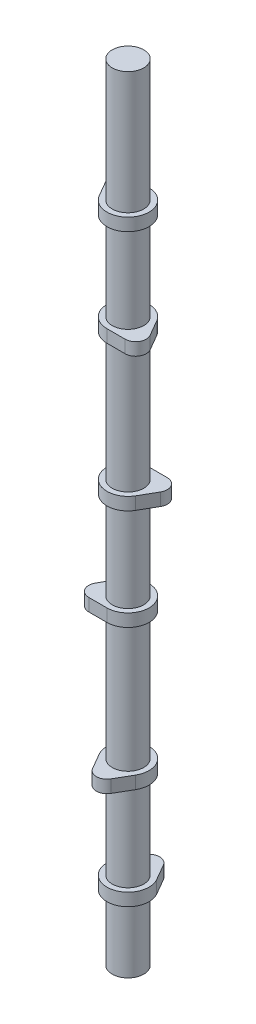
SolidWorks part; units mm, degrees
ref_plane "Front Plane" through (0, 0, 0) normal (0, 0, 1) x (1, 0, 0)
ref_plane "Top Plane" through (0, 0, 0) normal (0, 1, 0) x (1, 0, 0)
ref_plane "Right Plane" through (0, 0, 0) normal (1, 0, 0) x (0, 0, -1)
sketch "Sketch1" plane through (0, 0, 0) normal (0, 1, 0) x (1, 0, 0)
  line L0 (-5.4993, 15.875) -> (-10.9985, 6.35)
  line L1 (5.4993, 15.875) -> (10.9985, 6.35)
  arc A0 (-10.9985, 6.35) -> (10.9985, 6.35) centre (0, 0) ccw
  arc A1 (5.4993, 15.875) -> (-5.4993, 15.875) centre (0, 12.7) ccw
  dimension "D1" = 12.7
  dimension "D2" = 25.4
  dimension "D3" = 12.7
extrude "Boss-Extrude1" add sketch "Sketch1" along normal mid plane 7.62
ref_axis "Axis1" through (0, 49.7051, 0) along (0, -1, 0)
move or copy body "Body-Move/Copy1" bodies to move or copy 101 copy yes number of copies 1 translate (0, 60.96, 0)
move or copy body "Body-Move/Copy2" bodies to move or copy 102 copy no rotation origin (0, 0, 0) rotation axis (0, 1, 0) rotation angle 180
sketch "Sketch2" plane through (0, 0, 0) normal (0, 1, 0) x (1, 0, 0)
  circle A0 centre (0, 0) radius 9.5
  dimension "D1" = 19
extrude "Boss-Extrude2" add sketch "Sketch2" along normal blind 146.05 from offset 25.4 offset against normal yes
pattern_linear "LPattern1" count 3 spacing 146.05 along (0, 1, 0) of bodies 104
move or copy body "Body-Move/Copy3" bodies to move or copy 105 copy no rotation origin (0, 0, 0) rotation axis (0, 1, 0) rotation angle 120
move or copy body "Body-Move/Copy4" bodies to move or copy 106 copy no rotation origin (0, 0, 0) rotation axis (0, -1, 0) rotation angle 120
sketch "Sketch3" plane through (0, -25.4, 0) normal (0, -1, 0) x (1, 0, 0)
  circle A1 centre (0, 0) radius 9.5
  circle A2 centre (0, 0) radius 9.5
  dimension "D1" = 0
extrude "Boss-Extrude3" add sketch "Sketch3" along normal blind 17.94
combine bodies "Combine1" operation type add bodies to combine 109 107 108
sketch "Sketch4" plane through (0, 412.75, 0) normal (0, 1, 0) x (1, 0, 0)
  circle A1 centre (0, 0) radius 9.5
  circle A2 centre (0, 0) radius 9.5
  dimension "D1" = 0
extrude "Boss-Extrude4" add sketch "Sketch4" along normal blind 17.94
